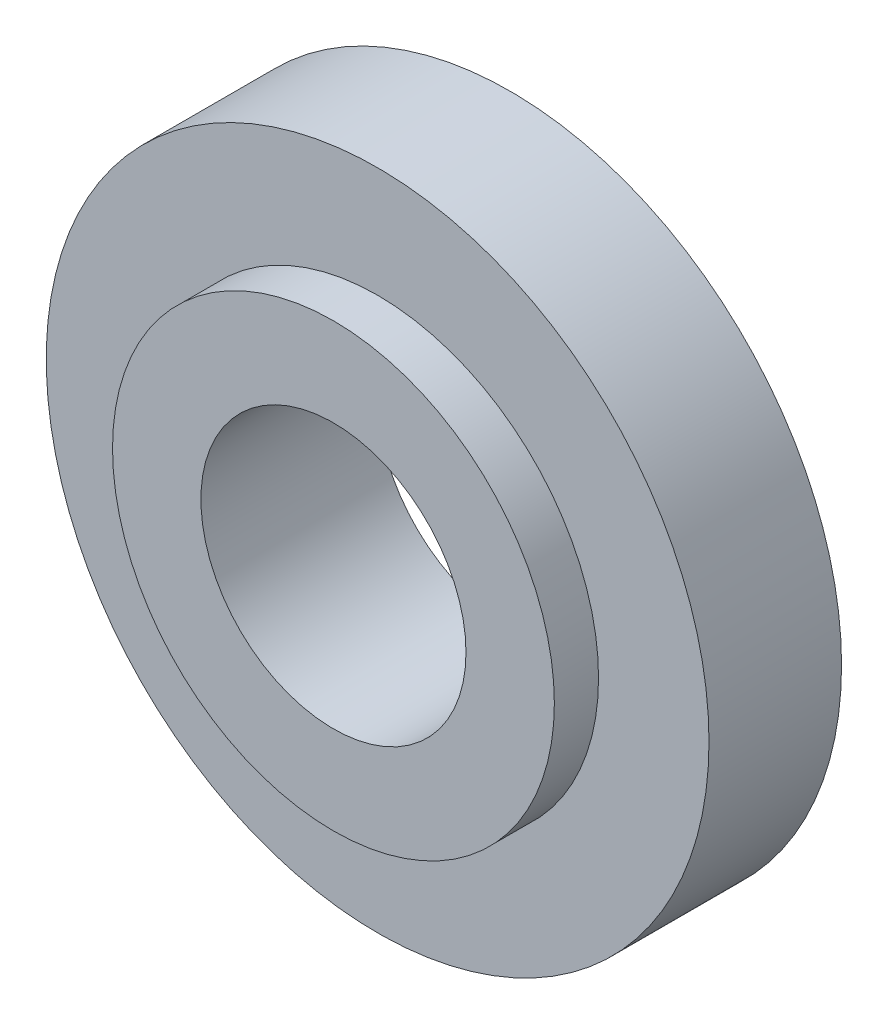
SolidWorks part; units mm, degrees
material "Nylon 101"
ref_plane "Front Plane" through (0, 0, 0) normal (0, 0, 1) x (1, 0, 0)
ref_plane "Top Plane" through (0, 0, 0) normal (0, 1, 0) x (1, 0, 0)
ref_plane "Right Plane" through (0, 0, 0) normal (1, 0, 0) x (0, 0, -1)
sketch "Sketch1" plane through (0, 0, 0) normal (0, 0, 1) x (1, 0, 0)
  circle A0 centre (0, 0) radius 3.75
  circle A1 centre (0, 0) radius 2.5
  circle A2 centre (0, 0) radius 1.5
  dimension "D1" = 7.5
  dimension "D2" = 5
  dimension "D3" = 3
extrude "Boss-Extrude1" add sketch "Sketch1" along normal blind 1.5 contours A0 A1 region at (-3.6439, 0, 0)
extrude "Boss-Extrude2" add sketch "Sketch1<3>" along normal blind 2 contours A1 A2 region at (-2.4293, 0, 0)
sketch "Sketch1<3>" plane through (0, 0, 0) normal (0, 0, 1) x (1, 0, 0) same geometry as "Sketch1"
